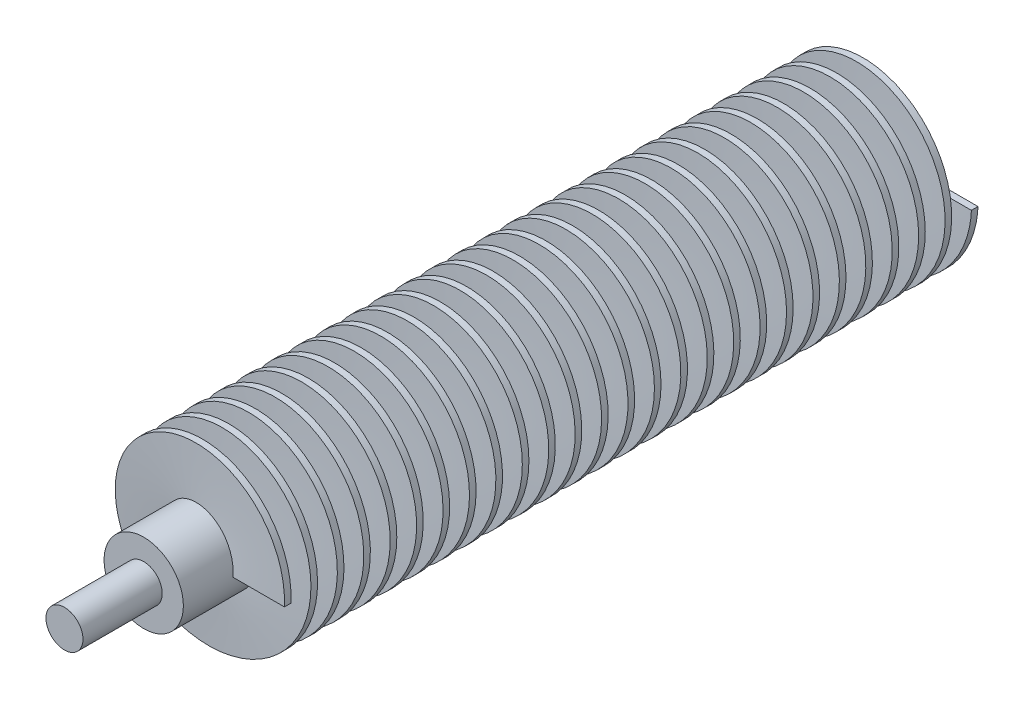
SolidWorks part; units mm, degrees
material "AISI 304"
ref_plane "Спереди" through (0, 0, 0) normal (0, 0, 1) x (1, 0, 0)
ref_plane "Сверху" through (0, 0, 0) normal (0, 1, 0) x (1, 0, 0)
ref_plane "Справа" through (0, 0, 0) normal (1, 0, 0) x (0, 0, -1)
ref_plane "Плоскость1" through (0, 0, -17) normal (0, 0, 1) x (1, 0, 0)
sketch "Эскиз1" plane through (0, 0, 0) normal (0, 0, 1) x (1, 0, 0)
  circle A0 centre (0, 0) radius 15
  dimension "D1" = 30
sketch "Эскиз2" plane through (0, 0, 0) normal (0, 1, 0) x (1, 0, 0)
  line L0 (15, 0) -> (-4.9813, 0) construction
  line L1 (15, 1.25) -> (34.5, 1.25)
  line L2 (15, 1.25) -> (15, -1.25)
  line L3 (15, -1.25) -> (34.5, -1.25)
  line L4 (34.5, 1.25) -> (34.5, -1.25)
  dimension "D1" = 2.5
  dimension "D2" = 15
  dimension "D3" = 34.5
curve "Спираль1" pitch 10 height 260 radius 15 left hand yes centre (0, 0, 0) axis (0, 0, -1) start towards (1, 0, 0)
sweep "По траектории1" add profiles "Эскиз2" path "Спираль1"
sketch "Эскиз3" plane through (0, 0, 0) normal (0, 1, 0) x (1, 0, 0)
  line L0 (0, -50) -> (7, -50)
  line L1 (7, -50) -> (7, -20)
  line L2 (7, -20) -> (15, -20)
  line L3 (15, -20) -> (15, 260)
  line L4 (15, 260) -> (0, 260)
  line L5 (0, 260) -> (0, -50)
  line L6 (0, -59.6319) -> (0, 170.3599) construction
  dimension "D1" = 310
  dimension "D2" = 50
  dimension "D3" = 30
  dimension "D4" = 14
revolve "Повернуть1" add sketch "Эскиз3" angle 360 mid plane about L6
sketch "Эскиз4" plane through (0, 0, 0) normal (1, 0, 0) x (0, 0, -1)
  line L0 (274.0415, 0) -> (145.9291, 0) construction
  line L1 (261.25, 0) -> (256.25, 0)
  line L2 (261.25, 0) -> (261.25, -20.7512)
  line L3 (261.25, -20.7512) -> (244.2693, -20.7512)
  line L4 (256.25, 0) -> (244.2693, -20.7512)
  spline S2 degree 2 number of poles 833 (1.25, 0) -> (261.25, 0) construction
  spline S3 degree 2 number of poles 829 (1.25, 0) -> (260, -10.6066) construction
  dimension "D1" = 60
revolve "Вырез-Повернуть1" cut sketch "Эскиз4" angle 360 mid plane about L0
